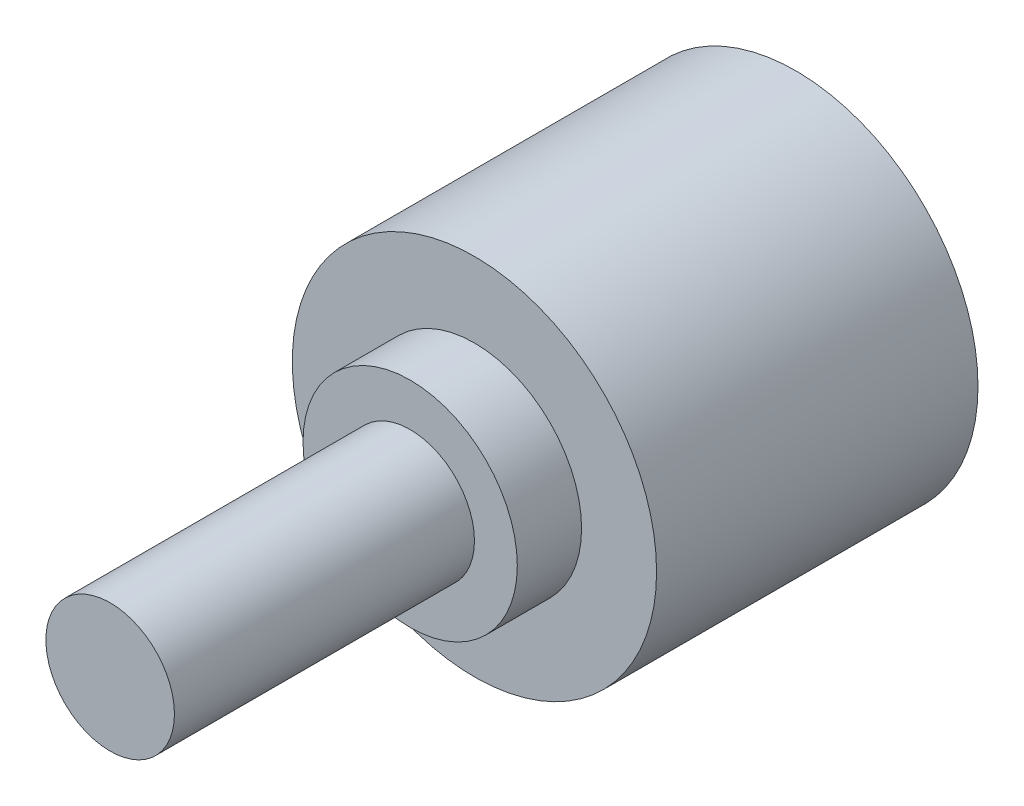
SolidWorks part; units mm, degrees
ref_plane "정면" through (0, 0, 0) normal (0, 0, 1) x (1, 0, 0)
ref_plane "윗면" through (0, 0, 0) normal (0, 1, 0) x (1, 0, 0)
ref_plane "우측면" through (0, 0, 0) normal (1, 0, 0) x (0, 0, -1)
sketch "스케치1" plane through (0, 0, 0) normal (0, 0, 1) x (1, 0, 0)
  circle A0 centre (0, 0) radius 8.5
  circle A1 centre (0, 0) radius 3
  circle A2 centre (0, 0) radius 5
  dimension "D1" = 17
  dimension "D2" = 6
  dimension "D3" = 10
extrude "보스-돌출1" add sketch "스케치1" along normal blind 14 contours A1 region at (0, 0, 0)
extrude "보스-돌출2" add sketch "스케치1<3>" against normal blind 3 contours A2
sketch "스케치1<3>" plane through (0, 0, 0) normal (0, 0, 1) x (1, 0, 0) same geometry as "스케치1"
extrude "보스-돌출3" add sketch "스케치1<4>" against normal blind 15 from surface contours A0 starting at face at (5, 0, -3)
sketch "스케치1<4>" plane through (0, 0, 0) normal (0, 0, 1) x (1, 0, 0) same geometry as "스케치1"
